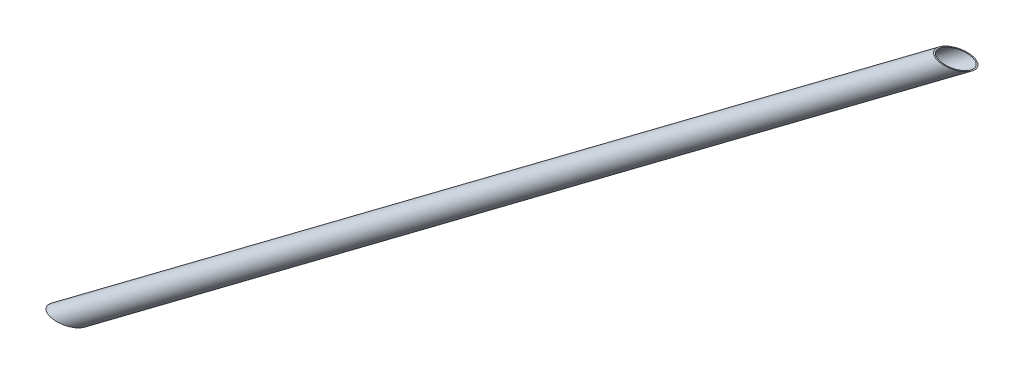
SolidWorks part; units mm, degrees
ref_plane "Alzado" through (0, 0, 0) normal (0, 0, 1) x (1, 0, 0)
ref_plane "Planta" through (0, 0, 0) normal (0, 1, 0) x (1, 0, 0)
ref_plane "Vista lateral" through (0, 0, 0) normal (1, 0, 0) x (0, 0, -1)
sketch "Croquis1" plane through (0, 0, 0) normal (0, 0, 1) x (1, 0, 0)
  line L1 (2000, 1500) -> (2000, 0) construction
  line L2 (0, 0) -> (2000, 0) construction
  line L3 (15.24, -20.32) -> (0, 0) construction
  line L14 (2000, 1500) -> (2015.24, 1479.68) construction
  line L15 (15.24, -20.32) -> (42.3333, 0) construction
  line L16 (2015.24, 1479.68) -> (2042.3333, 1500) construction
  line L19 (2042.3333, 1500) -> (2027.0933, 1520.32) construction
  line L20 (2027.0933, 1520.32) -> (0, 0) construction
  line L21 (2000, 1500) -> (2042.3333, 1500) construction
  line L22 (2042.3333, 1500) -> (15.24, -20.32)
  line L23 (15.24, -20.32) -> (14.04, -18.72)
  line L24 (14.04, -18.72) -> (2041.1333, 1501.6)
  line L25 (2041.1333, 1501.6) -> (2042.3333, 1500)
  dimension "D1" = 1500
  dimension "D2" = 2000
  dimension "D3" = 25.4
  dimension "D4" = 90
  dimension "D5" = 25.4
  dimension "D6" = 90
  dimension "D7" = 2
  dimension "D8" = 2
revolve "Revolución1" add sketch "Croquis1" angle 360 about L20
sketch "Croquis2" plane through (0, 0, 0) normal (0, 0, 1) x (1, 0, 0)
  line L0 (-15.24, 20.32) -> (69.4267, 20.32)
  line L1 (15.24, -20.32) -> (2042.3333, 1500) construction
  line L2 (69.4267, 20.32) -> (15.24, -20.32)
  line L3 (15.24, -20.32) -> (-15.24, 20.32)
  line L4 (2042.3333, 1500) -> (1957.6667, 1500)
  line L5 (2011.8533, 1540.64) -> (-15.24, 20.32) construction
  line L6 (1957.6667, 1500) -> (2011.8533, 1540.64)
  line L7 (2011.8533, 1540.64) -> (2042.3333, 1500)
extrude "Cortar-Extruir1" cut sketch "Croquis2" against normal through all and the other way through all contours L3 L0 L2 | L7 L4 L6
